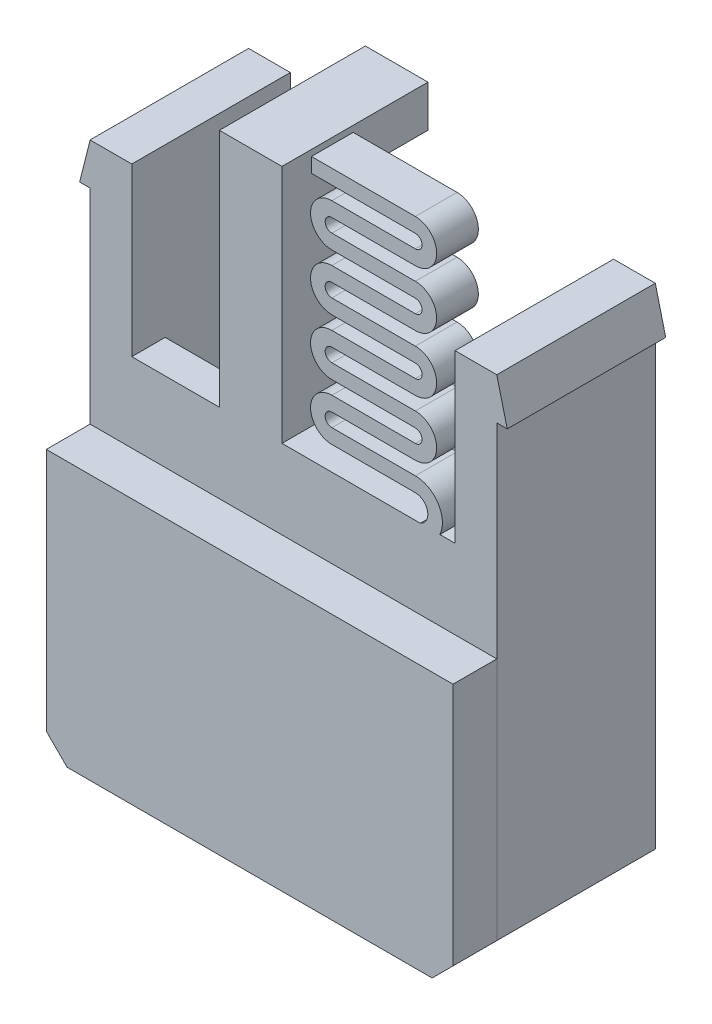
SolidWorks part; units mm, degrees
ref_plane "前视基准面" through (0, 0, 0) normal (0, 0, 1) x (1, 0, 0)
ref_plane "上视基准面" through (0, 0, 0) normal (0, 1, 0) x (1, 0, 0)
ref_plane "右视基准面" through (0, 0, 0) normal (1, 0, 0) x (0, 0, -1)
other "Configuration Table"
sketch "草图1" plane through (0, 0, 0) normal (0, 0, 1) x (1, 0, 0)
  line L0 (-63.9928, -19.7068) -> (-41.9928, -19.7068) construction
  line L1 (-62.7653, -7.0068) -> (-43.2653, -7.0068)
  line L2 (-62.7653, -7.0068) -> (-62.7653, -19.7068)
  line L3 (-62.7653, -19.7068) -> (-43.2653, -19.7068)
  line L4 (-43.2653, -7.0068) -> (-43.2653, -19.7068)
  dimension "D1" = 19.5
  dimension "D2" = 12.7
extrude "凸台-拉伸1" add sketch "草图1" along normal blind 2.1
sketch "草图2" plane through (0, 0, 0) normal (0, 0, -1) x (-1, 0, 0)
  line L1 (43.2653, -19.7068) -> (62.7653, -19.7068)
  line L2 (43.2653, -19.7068) -> (43.2653, 4.7932)
  line L3 (43.2653, 4.7932) -> (62.7653, 4.7932)
  line L4 (62.7653, -19.7068) -> (62.7653, 4.7932)
  dimension "D1" = 24.5
extrude "凸台-拉伸2" add sketch "草图2" along normal blind 7.6
sketch "草图3" plane through (0, 4.7932, 0) normal (0, 1, 0) x (1, 0, 0)
  line L0 (-62.7653, 7.6) -> (-43.2653, 7.6) construction
  line L1 (-60.7653, 7.6) -> (-45.2653, 7.6)
  line L2 (-60.7653, 7.6) -> (-60.7653, 1.6)
  line L3 (-60.7653, 1.6) -> (-45.2653, 1.6)
  line L4 (-45.2653, 7.6) -> (-45.2653, 1.6)
  line L5 (-62.7653, 7.6) -> (-62.7653, 0) construction
  line L6 (-43.2653, 7.6) -> (-43.2653, 0) construction
  dimension "D1" = 2
  dimension "D2" = 2
  dimension "D3" = 6
extrude "切除-拉伸1" cut sketch "草图3" against normal blind 23
sketch "草图4" plane through (0, 0, 0) normal (0, 0, 1) x (1, 0, 0)
  line L1 (-60.7653, 4.7932) -> (-45.2653, 4.7932)
  line L2 (-60.7653, 4.7932) -> (-60.7653, -3.2068)
  line L3 (-60.7653, -3.2068) -> (-45.2653, -3.2068)
  line L4 (-45.2653, 4.7932) -> (-45.2653, -3.2068)
  dimension "D1" = 8
extrude "切除-拉伸2" cut sketch "草图4" against normal up to next
sketch "草图5" plane through (0, 0, -7.6) normal (0, 0, -1) x (-1, 0, 0)
  line L0 (62.7653, 4.7932) -> (63.2653, 2.7932)
  line L1 (63.2653, 2.7932) -> (62.7653, 2.7932)
  line L2 (62.7653, -19.7068) -> (62.7653, 4.7932) construction
  line L3 (62.7653, 2.7932) -> (62.7653, 4.7932)
  line L4 (43.2653, 4.7932) -> (42.7653, 2.7932)
  line L5 (42.7653, 2.7932) -> (43.2653, 2.7932)
  line L6 (43.2653, 4.7932) -> (43.2653, -19.7068) construction
  line L7 (43.2653, 2.7932) -> (43.2653, 4.7932)
  dimension "D1" = 2
  dimension "D2" = 0.5
extrude "凸台-拉伸4" add sketch "草图5" against normal up to surface (7.6 mm away) up to face at (-53.0153, -0.1568, 0)
sketch "草图7" plane through (0, 0, 0) normal (0, 0, 1) x (1, 0, 0)
  line L0 (-47.1711, -1.7068) -> (-51.1711, -1.7068) construction
  line L1 (-60.7653, -3.2068) -> (-45.2653, -3.2068) construction
  line L2 (-47.1711, -0.3606) -> (-51.1711, -0.3606) construction
  line L3 (-47.1711, 0.9857) -> (-51.1711, 0.9857) construction
  line L4 (-47.1711, 2.3319) -> (-51.1711, 2.3319) construction
  line L5 (-47.1711, 3.6782) -> (-51.1711, 3.6782) construction
  line L6 (-47.1711, 5.0244) -> (-51.1711, 5.0244) construction
  line L7 (-47.1711, 6.3707) -> (-51.1711, 6.3707) construction
  line L8 (-47.1711, 7.7169) -> (-51.1711, 7.7169) construction
  line L9 (-47.1711, 9.0632) -> (-51.1711, 9.0632) construction
  line L10 (-47.1711, -1.3568) -> (-51.1711, -1.3568)
  line L11 (-47.1711, -0.7106) -> (-51.1711, -0.7106)
  line L12 (-47.1711, 1.3357) -> (-51.1711, 1.3357)
  line L13 (-47.1711, 1.9819) -> (-51.1711, 1.9819)
  line L14 (-47.1711, 4.0282) -> (-51.1711, 4.0282)
  line L15 (-47.1711, 4.6744) -> (-51.1711, 4.6744)
  line L16 (-47.1711, 6.7207) -> (-51.1711, 6.7207)
  line L17 (-47.1711, 7.3669) -> (-51.1711, 7.3669)
  line L18 (-47.1711, 9.4132) -> (-52.1509, 9.4132)
  line L19 (-47.1711, -2.0568) -> (-51.1711, -2.0568)
  line L20 (-47.1711, -0.0106) -> (-51.1711, -0.0106)
  line L21 (-47.1711, 0.6357) -> (-51.1711, 0.6357)
  line L22 (-47.1711, 2.6819) -> (-51.1711, 2.6819)
  line L23 (-47.1711, 3.3282) -> (-51.1711, 3.3282)
  line L24 (-47.1711, 5.3744) -> (-51.1711, 5.3744)
  line L25 (-47.1711, 6.0207) -> (-51.1711, 6.0207)
  line L26 (-47.1711, 8.0669) -> (-51.1711, 8.0669)
  line L27 (-47.1711, 8.7132) -> (-52.1509, 8.7132)
  line L28 (-47.1711, 9.0632) -> (-51.1407, 9.0632) construction
  line L29 (-47.1711, 8.7132) -> (-51.1407, 8.7132) construction
  line L30 (-47.1711, 9.4132) -> (-51.1407, 9.4132) construction
  line L31 (-72.3676, 9.4132) -> (-44.6127, 9.4132) construction
  line L32 (-52.1509, 9.4132) -> (-52.1509, 8.7132)
  line L33 (-46.9314, -3.2068) -> (-47.3969, -3.9371)
  arc A0 (-47.1711, -1.7068) -> (-46.3965, -3.2068) centre (-47.1711, -2.6568) cw construction
  arc A1 (-51.1711, -0.3606) -> (-51.1711, -1.7068) centre (-51.1711, -1.0337) ccw construction
  arc A2 (-47.1711, -0.3606) -> (-47.1711, 0.9857) centre (-47.1711, 0.3125) ccw construction
  arc A3 (-51.1711, 0.9857) -> (-51.1711, 2.3319) centre (-51.1711, 1.6588) cw construction
  arc A4 (-47.1711, 2.3319) -> (-47.1711, 3.6782) centre (-47.1711, 3.005) ccw construction
  arc A5 (-51.1711, 3.6782) -> (-51.1711, 5.0244) centre (-51.1711, 4.3513) cw construction
  arc A6 (-47.1711, 5.0244) -> (-47.1711, 6.3707) centre (-47.1711, 5.6975) ccw construction
  arc A7 (-51.1711, 6.3707) -> (-51.1711, 7.7169) centre (-51.1711, 7.0438) cw construction
  arc A8 (-47.1711, 7.7169) -> (-47.1711, 9.0632) centre (-47.1711, 8.39) ccw construction
  arc A9 (-47.1711, -1.3568) -> (-47.3969, -3.9371) centre (-47.1711, -2.6568) cw
  arc A10 (-51.1711, -0.7106) -> (-51.1711, -1.3568) centre (-51.1711, -1.0337) ccw
  arc A11 (-47.1711, -0.7106) -> (-47.1711, 1.3357) centre (-47.1711, 0.3125) ccw
  arc A12 (-51.1711, 1.3357) -> (-51.1711, 1.9819) centre (-51.1711, 1.6588) cw
  arc A13 (-47.1711, 1.9819) -> (-47.1711, 4.0282) centre (-47.1711, 3.005) ccw
  arc A14 (-51.1711, 4.0282) -> (-51.1711, 4.6744) centre (-51.1711, 4.3513) cw
  arc A15 (-47.1711, 4.6744) -> (-47.1711, 6.7207) centre (-47.1711, 5.6975) ccw
  arc A16 (-51.1711, 6.7207) -> (-51.1711, 7.3669) centre (-51.1711, 7.0438) cw
  arc A17 (-47.1711, 7.3669) -> (-47.1711, 9.4132) centre (-47.1711, 8.39) ccw
  arc A18 (-47.1711, -2.0568) -> (-46.9314, -3.2068) centre (-47.1711, -2.6568) cw
  arc A19 (-51.1711, -0.0106) -> (-51.1711, -2.0568) centre (-51.1711, -1.0337) ccw
  arc A20 (-47.1711, -0.0106) -> (-47.1711, 0.6357) centre (-47.1711, 0.3125) ccw
  arc A21 (-51.1711, 0.6357) -> (-51.1711, 2.6819) centre (-51.1711, 1.6588) cw
  arc A22 (-47.1711, 2.6819) -> (-47.1711, 3.3282) centre (-47.1711, 3.005) ccw
  arc A23 (-51.1711, 3.3282) -> (-51.1711, 5.3744) centre (-51.1711, 4.3513) cw
  arc A24 (-47.1711, 5.3744) -> (-47.1711, 6.0207) centre (-47.1711, 5.6975) ccw
  arc A25 (-51.1711, 6.0207) -> (-51.1711, 8.0669) centre (-51.1711, 7.0438) cw
  arc A26 (-47.1711, 8.0669) -> (-47.1711, 8.7132) centre (-47.1711, 8.39) ccw
  arc A27 (-47.1711, -1.7068) -> (-47.3361, -3.5924) centre (-47.1711, -2.6568) cw construction
  arc A28 (-47.1711, -2.0568) -> (-47.2753, -3.2477) centre (-47.1711, -2.6568) cw construction
  dimension "D1" = 4
  dimension "D2" = 1.5
  dimension "D4" = 0.35
  dimension "D5" = 0.35
  dimension "D3" = 9
extrude "凸台-拉伸5" add sketch "草图7" against normal blind 2
sketch "草图8" plane through (0, -3.2068, 0) normal (0, 1, 0) x (1, 0, 0)
  line L0 (-60.7653, 0) -> (-46.9314, 0) construction
  line L1 (-56.5653, 0) -> (-53.5653, 0)
  line L2 (-56.5653, 0) -> (-56.5653, 3)
  line L3 (-56.5653, 3) -> (-53.5653, 3)
  line L4 (-53.5653, 0) -> (-53.5653, 3)
  line L5 (-60.7653, 1.6) -> (-60.7653, 0) construction
  dimension "D1" = 4.2
  dimension "D2" = 3
  dimension "D3" = 3
extrude "凸台-拉伸6" add sketch "草图8" along normal blind 11.5 and the other way blind 4
sketch "草图9" plane through (0, 0, -3) normal (0, 0, -1) x (-1, 0, 0)
  line L0 (56.5653, -7.2068) -> (56.5653, 8.2932) construction
  line L1 (53.5653, 8.2932) -> (56.5653, 8.2932)
  line L2 (53.5653, 8.2932) -> (53.5653, 6.2932)
  line L3 (53.5653, 6.2932) -> (56.5653, 6.2932)
  line L4 (56.5653, 8.2932) -> (56.5653, 6.2932)
  dimension "D1" = 2
extrude "凸台-拉伸7" add sketch "草图9" along normal blind 4
chamfer "倒角1" distance 1 angle 45 2 edges at (-62.7653, -19.7068, -2.75) (-43.2653, -19.7068, -2.75)
split "分割1" bodies to split 114 resulting bodies 115 116 split by face at (-50.3799, 2.7132, 0)
